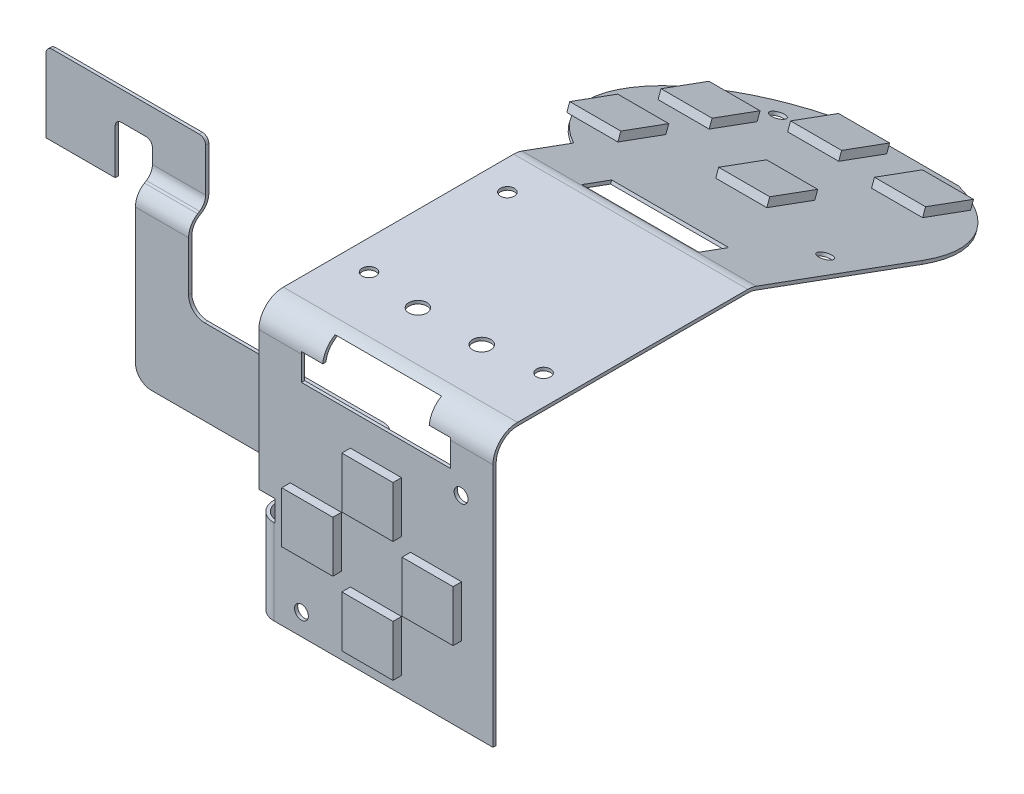
SolidWorks part; units mm, degrees
ref_plane "前视基准面" through (0, 0, 0) normal (0, 0, 1) x (1, 0, 0)
ref_plane "上视基准面" through (0, 0, 0) normal (0, 1, 0) x (1, 0, 0)
ref_plane "右视基准面" through (0, 0, 0) normal (1, 0, 0) x (0, 0, -1)
other "Configuration Table"
sketch "草图1" plane through (0, 0, 0) normal (1, 0, 0) x (0, 0, -1)
  line L0 (0, -25) -> (0, -2)
  line L1 (2, 0) -> (23.6457, 0)
  line L2 (24.3327, -0.1217) -> (52.1746, -10.3049)
  line L3 (-0.3, -25) -> (-0.3, -2)
  line L4 (2, 0.3) -> (23.6457, 0.3)
  line L5 (24.4358, 0.1601) -> (52.2777, -10.0231)
  line L6 (0, -25) -> (-0.3, -25)
  line L7 (52.2777, -10.0231) -> (52.1746, -10.3049)
  arc A0 (23.6457, 0) -> (24.3327, -0.1217) centre (23.6457, -2) cw
  arc A1 (0, -2) -> (2, 0) centre (2, -2) cw
  arc A2 (-0.3, -2) -> (2, 0.3) centre (2, -2) cw
  arc A3 (23.6457, 0.3) -> (24.4358, 0.1601) centre (23.6457, -2) cw
  point P7 (24, 0)
  point P10 (0, 0)
  dimension "D5" = 2
  dimension "D1" = 25
  dimension "D2" = 24
  dimension "D3" = 159.91
  dimension "D4" = 30
  dimension "D6" = 0.3
extrude "凸台-拉伸1" add sketch "草图1" along normal blind 22
sketch "草图2" plane through (0, 0, 0.3) normal (0, 0, 1) x (1, 0, 0)
  line L0 (22, 0.3) -> (0, 0.3) construction
  line L1 (4, -4.3) -> (18, -4.3)
  line L2 (4, -4.3) -> (4, -1.8)
  line L3 (4, -1.8) -> (18, -1.8)
  line L4 (18, -4.3) -> (18, -1.8)
  line L5 (6, -1.8) -> (16, -1.8)
  line L6 (6, -1.8) -> (6, 0)
  line L7 (6, 0) -> (16, 0)
  line L8 (16, -1.8) -> (16, 0)
  line L10 (11, -26.5654) -> (11, 3.7124) construction
  line L12 (0, -2) -> (0, -25) construction
  line L13 (22, -2) -> (22, -25) construction
  line M13 (22, -2) -> (0, -2)
  dimension "D1" = 1.8
  dimension "D2" = 2.5
  dimension "D3" = 0.3
  dimension "D4" = 14
  dimension "D5" = 10
extrude "切除-拉伸1" cut sketch "草图2" against normal blind 4 contours L3 L10 L7 L6 | L10 L5 L8 L7 | L1 L10 L2 M13 | L10 L1 L4 M13 | L10 L3 L2 M13 | L10 L4 L3 L5 M13 region at (7.5, -3.15, 0.3) region at (14.5, -3.15, 0.3) region at (7.5, -1.9, 0.3) region at (14.5, -1.9, 0.3) region at (13.5, -0.9, 0.3) region at (8.5, -0.9, 0.3)
sketch "草图3" plane through (0, 8.024, -2.9348) normal (0, 0.9392, -0.3435) x (1, 0, 0)
  line L0 (22, 52.5397) -> (22, 22.894) construction
  line L1 (22, 52.5397) -> (0, 52.5397) construction
  circle A0 centre (8, 39.5397) radius 14
  line M2 (0, 52.5397) -> (0, 22.894)
  line M4 (22, 22.894) -> (22, 52.5397)
  line M5 (22, 52.5397) -> (0, 52.5397)
  dimension "D1" = 28
  dimension "D2" = 13
extrude "切除-拉伸2" cut sketch "草图3" against normal through all contours A0 M4 M5 | A0 M5 M2 region at (19.6053, -8.9881, -49.4478) region at (0.8895, -9.8577, -51.8254)
extrude "凸台-拉伸2" add sketch "草图3<3>" against normal blind 0.3
sketch "草图3<3>" plane through (0, 8.024, -2.9348) normal (0, 0.9392, -0.3435) x (1, 0, 0) same geometry as "草图3"
sketch "草图4" plane through (0, 0, 0.3) normal (0, 0, 1) x (1, 0, 0)
  line L0 (-5.9466, -15.4) -> (23.7502, -15.4) construction
  line L1 (8.6, -7.35) -> (13.4, -7.35)
  line L2 (8.6, -7.35) -> (8.6, -12.15)
  line L3 (8.6, -12.15) -> (13.4, -12.15)
  line L4 (13.4, -7.35) -> (13.4, -12.15)
  line L5 (11, -28.2671) -> (11, 2.5503) construction
  line L6 (0, -2) -> (0, -25) construction
  line L7 (22, -2) -> (22, -25) construction
  line L8 (22, -25) -> (0, -25) construction
  line L9 (8.6, -18.65) -> (13.4, -18.65)
  line L10 (8.6, -18.65) -> (8.6, -23.45)
  line L11 (8.6, -23.45) -> (13.4, -23.45)
  line L12 (13.4, -18.65) -> (13.4, -23.45)
  line L14 (2.95, -13) -> (7.75, -13)
  line L15 (2.95, -13) -> (2.95, -17.8)
  line L16 (2.95, -17.8) -> (7.75, -17.8)
  line L17 (7.75, -13) -> (7.75, -17.8)
  line L18 (14.25, -13) -> (19.05, -13)
  line L19 (14.25, -13) -> (14.25, -17.8)
  line L20 (14.25, -17.8) -> (19.05, -17.8)
  line L21 (19.05, -13) -> (19.05, -17.8)
  dimension "D1" = 4.8
  dimension "D2" = 9.6
  dimension "D3" = 6.5
  dimension "D4" = 6.5
extrude "凸台-拉伸3" add sketch "草图4" along normal blind 0.8
sketch "草图5" plane through (0, 0.3, 0) normal (0, 1, 0) x (1, 0, 0)
  line L0 (11, -6.2283) -> (11, 16.6274) construction
  line L3 (0, 23.6457) -> (0, 2) construction
  line L4 (22, 23.6457) -> (22, 2) construction
  line L5 (22, 23.6457) -> (0, 23.6457) construction
  circle A0 centre (8, 6.6457) radius 0.85
  circle A1 centre (14, 6.6457) radius 0.85
  dimension "D1" = 1.7
  dimension "D2" = 17
  dimension "D3" = 3
extrude "切除-拉伸3" cut sketch "草图5" against normal through all
sketch "草图6" plane through (0, 8.024, -2.9348) normal (0, 0.9392, -0.3435) x (1, 0, 0)
  line L0 (11, 16.3664) -> (11, 30.7303) construction
  line L1 (5.5, 23) -> (16.5, 23)
  line L2 (5.5, 23) -> (5.5, 26)
  line L3 (5.5, 26) -> (16.5, 26)
  line L4 (16.5, 23) -> (16.5, 26)
  line L7 (0, 22.1039) -> (0, 1.7753) construction
  line L8 (22, 22.1039) -> (22, 1.7753) construction
  dimension "D1" = 11
  dimension "D2" = 3
  dimension "D3" = 23
extrude "切除-拉伸4" cut sketch "草图6" against normal blind 1
sketch "草图7" plane through (0, 8.024, -2.9348) normal (0, 0.9392, -0.3435) x (1, 0, 0)
  line L1 (7.3385, 34.4514) -> (12.1385, 34.4514)
  line L2 (7.3385, 34.4514) -> (7.3385, 39.2514)
  line L3 (7.3385, 39.2514) -> (12.1385, 39.2514)
  line L4 (12.1385, 34.4514) -> (12.1385, 39.2514)
  line L5 (11.7188, 45.3744) -> (16.5188, 45.3744)
  line L6 (11.7188, 45.3744) -> (11.7188, 50.1744)
  line L7 (11.7188, 50.1744) -> (16.5188, 50.1744)
  line L8 (16.5188, 45.3744) -> (16.5188, 50.1744)
  line L9 (7.6196, 46.4557) -> (2.8196, 46.4557)
  line L10 (7.6196, 46.4557) -> (7.6196, 51.2557)
  line L11 (7.6196, 51.2557) -> (2.8196, 51.2557)
  line L12 (2.8196, 46.4557) -> (2.8196, 51.2557)
  line L13 (0.9105, 40.6376) -> (-3.8895, 40.6376)
  line L14 (0.9105, 40.6376) -> (0.9105, 45.4376)
  line L15 (0.9105, 45.4376) -> (-3.8895, 45.4376)
  line L16 (-3.8895, 40.6376) -> (-3.8895, 45.4376)
  line L17 (0.748, 31.6791) -> (-4.052, 31.6791)
  line L18 (0.748, 31.6791) -> (0.748, 36.4791)
  line L19 (0.748, 36.4791) -> (-4.052, 36.4791)
  line L20 (-4.052, 31.6791) -> (-4.052, 36.4791)
  dimension "D1" = 4.8
extrude "凸台-拉伸4" add sketch "草图7" along normal blind 0.8
sketch "草图9" plane through (0, -25, 0) normal (0, -1, 0) x (1, 0, 0)
  line L0 (22, 0.3) -> (0, 0.3) construction
  line L1 (0, 0) -> (1.5, 0)
  line L2 (0, 0) -> (0, 0.3)
  line L3 (0, 0.3) -> (1.5, 0.3)
  line L4 (1.5, 0) -> (1.5, 0.3)
  dimension "D1" = 1.5
extrude "切除-拉伸5" cut sketch "草图9" against normal blind 10
sketch "草图10" plane through (0, -25, 0) normal (0, -1, 0) x (1, 0, 0)
  line L0 (1.5, 0) -> (1.4, 0)
  line L1 (-0.1, -1.5) -> (-0.1, -11.5)
  line L2 (-1.6, -13) -> (-17.6, -13)
  line L3 (1.5, 0.3) -> (1.4, 0.3)
  line L4 (-0.4, -1.5) -> (-0.4, -11.5)
  line L5 (-1.6, -12.7) -> (-17.6, -12.7)
  line L6 (1.5, 0) -> (1.5, 0.3)
  line L7 (-17.6, -13) -> (-17.6, -12.7)
  arc A0 (1.4, 0) -> (-0.1, -1.5) centre (1.4, -1.5) ccw
  arc A1 (-0.1, -11.5) -> (-1.6, -13) centre (-1.6, -11.5) cw
  arc A2 (1.4, 0.3) -> (-0.4, -1.5) centre (1.4, -1.5) ccw
  arc A3 (-0.4, -11.5) -> (-1.6, -12.7) centre (-1.6, -11.5) cw
  point P8 (-0.1, 0)
  point P11 (-0.1, -13)
  dimension "D3" = 1.5
  dimension "D1" = 1.6
  dimension "D2" = 13
  dimension "D5" = 16
  dimension "D4" = 0.3
extrude "凸台-拉伸5" add sketch "草图10" against normal blind 8
sketch "草图11" plane through (0, 0, -12.7) normal (0, 0, 1) x (1, 0, 0)
  line L0 (-17.6, -17) -> (-17.6, -25)
  line L1 (-17.6, -25) -> (-23.1, -25)
  line L2 (-24.6, -23.5) -> (-24.6, -11)
  line L3 (-24.6, -11) -> (-19.6, -11)
  line L4 (-19.6, -11) -> (-19.6, -15.5)
  line L5 (-18.1, -17) -> (-17.6, -17)
  arc A0 (-23.1, -25) -> (-24.6, -23.5) centre (-23.1, -23.5) cw
  arc A1 (-19.6, -15.5) -> (-18.1, -17) centre (-18.1, -15.5) ccw
  point P10 (-24.6, -25)
  dimension "D4" = 1.5
  dimension "D1" = 7
  dimension "D2" = 14
  dimension "D3" = 5
extrude "凸台-拉伸6" add sketch "草图11" against normal blind 0.3
sketch "草图12" plane through (-24.6, 0, 0) normal (-1, 0, 0) x (0, 0, 1)
  line L0 (-13, -11) -> (-13, -10.8314)
  line L1 (-13.705, -9.5594) -> (-13.895, -9.4406)
  line L2 (-14.6, -8.1686) -> (-14.6, -8)
  line L3 (-12.7, -11) -> (-12.7, -10.8314)
  line L4 (-13.546, -9.305) -> (-13.736, -9.1862)
  line L5 (-14.3, -8.1686) -> (-14.3, -8)
  line L6 (-13, -11) -> (-12.7, -11)
  line L7 (-14.6, -8) -> (-14.3, -8)
  arc A0 (-13, -10.8314) -> (-13.705, -9.5594) centre (-14.5, -10.8314) ccw
  arc A1 (-13.895, -9.4406) -> (-14.6, -8.1686) centre (-13.1, -8.1686) cw
  arc A2 (-12.7, -10.8314) -> (-13.546, -9.305) centre (-14.5, -10.8314) ccw
  arc A3 (-13.736, -9.1862) -> (-14.3, -8.1686) centre (-13.1, -8.1686) cw
  point P8 (-13, -10)
  point P11 (-14.6, -9)
  dimension "D5" = 1.5
  dimension "D1" = 1
  dimension "D2" = 1
  dimension "D3" = 1.6
  dimension "D4" = 1
  dimension "D6" = 0.3
extrude "凸台-拉伸7" add sketch "草图12" against normal blind 5
sketch "草图13" plane through (0, 0, -14.3) normal (0, 0, 1) x (1, 0, 0)
  line L0 (-24.6, -8) -> (-19.6, -8)
  line L1 (-19.6, -8) -> (-19.6, -4.1)
  line L2 (-20.2, -3.5) -> (-34, -3.5)
  line L3 (-34.6, -4.1) -> (-34.6, -11)
  line L4 (-34.6, -11) -> (-28.1, -11)
  line L5 (-28.1, -11) -> (-28.1, -6.8)
  line L6 (-27.5, -6.2) -> (-25.2, -6.2)
  line L7 (-24.6, -6.8) -> (-24.6, -8)
  arc A0 (-34, -3.5) -> (-34.6, -4.1) centre (-34, -4.1) ccw
  arc A1 (-19.6, -4.1) -> (-20.2, -3.5) centre (-20.2, -4.1) ccw
  arc A2 (-25.2, -6.2) -> (-24.6, -6.8) centre (-25.2, -6.8) cw
  arc A3 (-28.1, -6.8) -> (-27.5, -6.2) centre (-27.5, -6.8) cw
  point P12 (-34.6, -3.5)
  point P15 (-19.6, -3.5)
  point P18 (-24.6, -6.2)
  dimension "D5" = 0.6
  dimension "D1" = 4.5
  dimension "D2" = 6.5
  dimension "D3" = 7.5
  dimension "D4" = 1.8
  dimension "D6" = 15
extrude "凸台-拉伸8" add sketch "草图13" against normal blind 0.3
sketch "草图14" plane through (0, 8.024, -2.9348) normal (0, 0.9392, -0.3435) x (1, 0, 0)
  line L0 (0, 28.0506) -> (0, 22.894) construction
  line L1 (2, 52.5506) -> (14, 52.5506)
  line L2 (2, 52.5506) -> (2, 54.5506)
  line L3 (2, 54.5506) -> (14, 54.5506)
  line L4 (14, 52.5506) -> (14, 54.5506)
  circle A0 centre (0.5, 47.9506) radius 0.65
  circle A1 centre (19.5, 32.4506) radius 0.65
  dimension "D5" = 1.3
  dimension "D1" = 12
  dimension "D2" = 2
  dimension "D3" = 24.5
  dimension "D4" = 2
  dimension "D6" = 0.5
  dimension "D7" = 19.9
  dimension "D8" = 19
  dimension "D9" = 15.5
extrude "切除-拉伸6" cut sketch "草图14" against normal blind 4
sketch "草图15" plane through (0, 0.3, 0) normal (0, 1, 0) x (1, 0, 0)
  line L0 (2.8, 18.5921) -> (2.8, 10.622) construction
  line L1 (15.631, 7.25) -> (4.6393, 7.25) construction
  line L4 (11, -5.7583) -> (11, 19.5262) construction
  line L5 (0, 23.6457) -> (0, 2) construction
  line L6 (22, 23.6457) -> (22, 2) construction
  line L7 (22, 2) -> (0, 2) construction
  circle A0 centre (2.8, 20.25) radius 0.65
  circle A1 centre (2.8, 7.25) radius 0.65
  circle A2 centre (19.2, 7.25) radius 0.65
  dimension "D1" = 1.3
  dimension "D2" = 13
  dimension "D3" = 16.4
  dimension "D4" = 5.25
extrude "切除-拉伸7" cut sketch "草图15" against normal blind 4
sketch "草图16" plane through (0, 0, 0.3) normal (0, 0, 1) x (1, 0, 0)
  line L0 (22, -2) -> (22, -25) construction
  line L1 (22, -2) -> (18, -2) construction
  circle A0 centre (19, -6) radius 0.65
  circle A1 centre (4, -23) radius 0.65
  dimension "D1" = 1.3
  dimension "D2" = 3
  dimension "D3" = 4
  dimension "D4" = 15
  dimension "D5" = 17
extrude "切除-拉伸8" cut sketch "草图16" against normal blind 4
